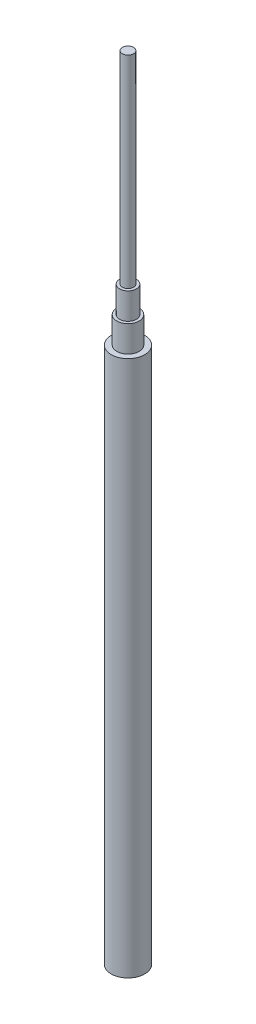
SolidWorks part; units mm, degrees
material "Plain Carbon Steel"
ref_plane "Front Plane" through (0, 0, 0) normal (0, 0, 1) x (1, 0, 0)
ref_plane "Top Plane" through (0, 0, 0) normal (0, 1, 0) x (1, 0, 0)
ref_plane "Right Plane" through (0, 0, 0) normal (1, 0, 0) x (0, 0, -1)
sketch "Sketch1" plane through (0, 0, 0) normal (0, 1, 0) x (1, 0, 0)
  circle A0 centre (0, 0) radius 4.7625
  dimension "D1" = 9.525
extrude "Boss-Extrude1" add sketch "Sketch1" along normal blind 152.5
sketch "Sketch2" plane through (0, 0, 0) normal (0, 1, 0) x (1, 0, 0)
  circle A0 centre (0, 0) radius 3.175
  dimension "D1" = 6.35
extrude "Boss-Extrude2" add sketch "Sketch2" along normal blind 160
sketch "Sketch3" plane through (0, 0, 0) normal (0, 1, 0) x (1, 0, 0)
  circle A0 centre (0, 0) radius 2.3812
  dimension "D1" = 4.7625
extrude "Boss-Extrude3" add sketch "Sketch3" along normal blind 167.5
sketch "Sketch4" plane through (0, 0, 0) normal (0, 1, 0) x (1, 0, 0)
  circle A0 centre (0, 0) radius 1.5875
  dimension "D1" = 3.175
extrude "Boss-Extrude4" add sketch "Sketch4" along normal blind 225
